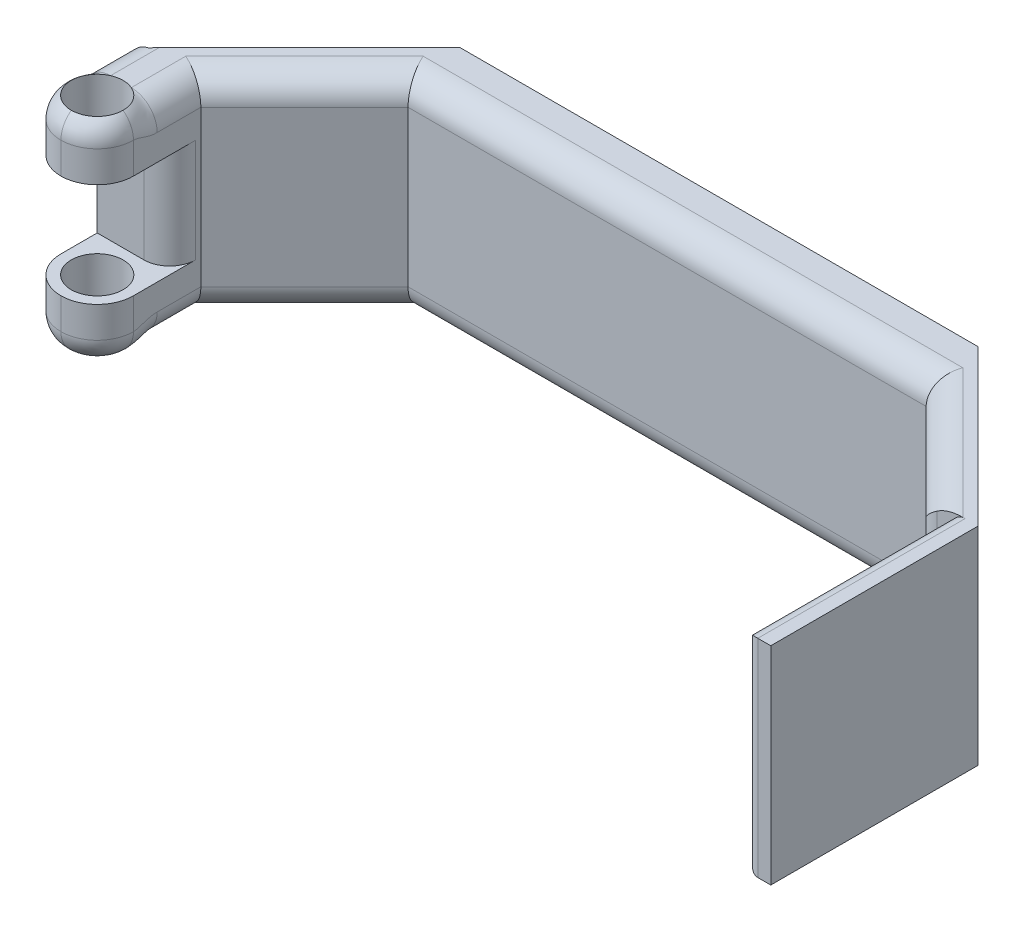
SolidWorks part; units mm, degrees
ref_plane "Front Plane" through (0, 0, 0) normal (0, 0, 1) x (1, 0, 0)
ref_plane "Top Plane" through (0, 0, 0) normal (0, 1, 0) x (1, 0, 0)
ref_plane "Right Plane" through (0, 0, 0) normal (1, 0, 0) x (0, 0, -1)
sketch "Sketch1" plane through (0, 0, 0) normal (0, 1, 0) x (1, 0, 0)
  line L0 (0, 0) -> (20, 20)
  line L1 (20, 20) -> (120, 20)
  line L2 (120, 20) -> (140, 0)
  line L3 (0, 0) -> (-10, 0)
  line L4 (-10, 0) -> (20, 30)
  line L5 (20, 30) -> (120, 30)
  line L6 (140, 0) -> (150, 0)
  line L7 (150, 0) -> (120, 30)
  dimension "D1" = 20
  dimension "D2" = 20
  dimension "D3" = 100
  dimension "D4" = 20
  dimension "D5" = 20
  dimension "D6" = 10
  dimension "D7" = 10
  dimension "D8" = 10
extrude "Boss-Extrude1" add sketch "Sketch1" along normal blind 40
sketch "Sketch2" plane through (0, 0, 0) normal (0, 0, 1) x (1, 0, 0)
  line L1 (0, 40) -> (-14, 40)
  line L2 (0, 40) -> (0, 0)
  line L3 (0, 0) -> (-14, 0)
  line L4 (-14, 40) -> (-14, 0)
  dimension "D1" = 14
extrude "Boss-Extrude2" add sketch "Sketch2" along normal blind 20
sketch "Sketch3" plane through (0, 0, 0) normal (1, 0, 0) x (0, 0, -1)
  line L0 (-20, 0) -> (-20, 40) construction
  line L1 (-20, 30) -> (-6, 30)
  line L2 (-20, 30) -> (-20, 10)
  line L3 (-20, 10) -> (-6, 10)
  line L4 (-6, 30) -> (-6, 10)
  line L5 (-20, 0) -> (0, 0) construction
  dimension "D1" = 14
  dimension "D2" = 20
  dimension "D3" = 10
extrude "Cut-Extrude2" cut sketch "Sketch3" against normal up to next
sketch "Sketch5" plane through (0, 10, 0) normal (0, 1, 0) x (1, 0, 0)
  circle A0 centre (-7, -13) radius 5
  dimension "D1" = 10
extrude "Cut-Extrude3" cut sketch "Sketch5" against normal through all and the other way through all
fillet "Fillet1" radius 7 4 edges at (-14, 5, 20) (0, 5, 20) (0, 35, 20) (-14, 35, 20)
sketch "Sketch7" plane through (0, 0, 0) normal (0, 0, 1) x (1, 0, 0)
  line L0 (140, 0) -> (150, 0) construction
  line L1 (150, 40) -> (145, 40)
  line L2 (150, 40) -> (150, 0)
  line L3 (150, 0) -> (145, 0)
  line L4 (145, 40) -> (145, 0)
extrude "Boss-Extrude3" add sketch "Sketch7" along normal blind 40
fillet "Fillet2" radius 5 12 edges at (0, 0, 6.5) (-14, 0, 6.5) (-14, 40, 6.5) (0, 40, 6.5) (0, 20, 6) (140, 20, 0) (130, 40, -10) (130, 0, -10) (70, 0, -20) (10, 0, -10) (70, 40, -20) (10, 40, -10)
fillet "Fillet3" radius 2.5 3 edges at (145, 20, 40) (145, 0, 18.9645) (145, 40, 18.9645)
